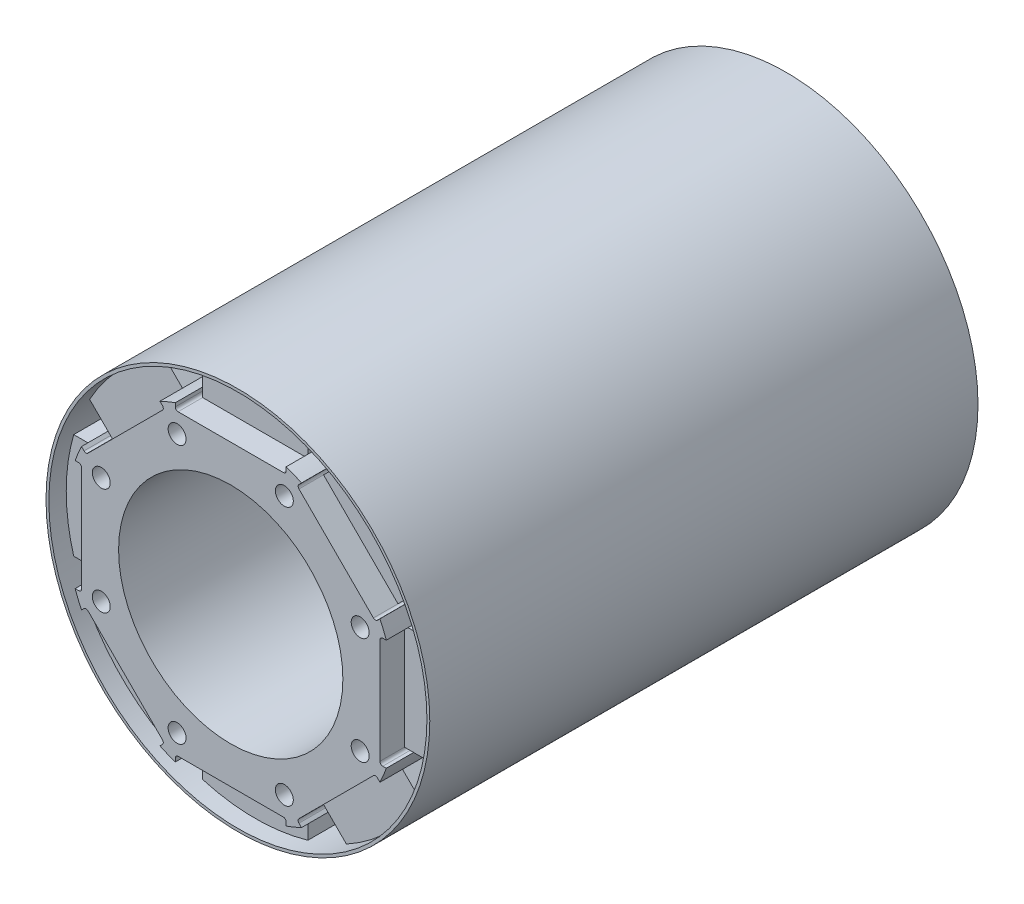
SolidWorks part; units mm, degrees
ref_plane "前视基准面" through (0, 0, 0) normal (0, 0, 1) x (1, 0, 0)
ref_plane "上视基准面" through (0, 0, 0) normal (0, 1, 0) x (1, 0, 0)
ref_plane "右视基准面" through (0, 0, 0) normal (1, 0, 0) x (0, 0, -1)
sketch "草图1" plane through (0, 0, 0) normal (0, 0, 1) x (1, 0, 0)
  circle A0 centre (0, 0) radius 14.735
  circle A1 centre (0, 0) radius 10.005
  dimension "D1" = 29.47
  dimension "D2" = 20.01
extrude "凸台-拉伸1" add sketch "草图1" along normal blind 50.19
ref_plane "基准面1" through (0, 0, 3) normal (0, 0, -1) x (-1, 0, 0)
sketch "草图3" plane through (0, 0, 3) normal (0, 0, -1) x (-1, 0, 0)
  line L0 (0, 17.0863) -> (0, -17.5115) construction
  line L1 (-4.9475, 13.8796) -> (-4.9475, 13.31)
  line L2 (-4.9475, 13.31) -> (4.9475, 13.31)
  line L3 (4.9475, 13.31) -> (4.9475, 13.8796)
  arc A0 (4.9475, 13.8796) -> (-4.9475, 13.8796) centre (0, 0) ccw
  dimension "D2" = 14.735
  dimension "D1" = 13.31
  dimension "D3" = 9.895
extrude "切除-拉伸1" cut sketch "草图3" against normal through all and the other way blind 42 contours L2 L3 A0 L1
ref_axis "基准轴1" through (0, 0, 50.19) along (0, 0, -1)
fillet "圆角1" radius 0.25 2 edges at (-4.9475, 13.31, 25.095) (4.9475, 13.31, 25.095)
pattern_circular "阵列(圆周)2" count 8 over 360 about axis through (0, 0, 50.19) along (0, 0, -1) of "圆角1", "切除-拉伸1"
sketch "草图4" plane through (0, 0, 3) normal (0, 0, -1) x (-1, 0, 0)
  line L0 (0, 0) -> (0, 19.0796) construction
  line L1 (-4.6975, 13.31) -> (-4.6975, 16.1976)
  line L2 (-4.6975, 13.31) -> (4.6975, 13.31)
  line L3 (4.6975, 13.31) -> (4.6975, 16.1976)
  arc A0 (4.6975, 16.1976) -> (-4.6975, 16.1976) centre (0, 0) ccw
  dimension "D1" = 33.73
extrude "凸台-拉伸2" add sketch "草图4" against normal blind 45
pattern_circular "阵列(圆周)4" count 8 over 360 about axis through (0, 0, 50.19) along (0, 0, -1) of "凸台-拉伸2"
ref_plane "基准面2" through (0, 0, 0.64) normal (0, 0, -1) x (-1, 0, 0)
sketch "草图5" plane through (0, 0, 0.64) normal (0, 0, -1) x (-1, 0, 0)
  circle A0 centre (0, 0) radius 16.865
  circle A1 centre (0, 0) radius 17.12
  dimension "D1" = 34.24
extrude "凸台-拉伸3" add sketch "草图5" against normal offset from surface (48.91 mm away) 0.64 up to face at (10.005, 0, 50.19)
hole_wizard "M2 螺纹孔2" positions "草图10" profile "草图9" tap size "M2" standard "GB"
sketch "草图10" plane through (0, 0, 50.19) normal (0, 0, 1) x (1, 0, 0)
  line L0 (0, 0) -> (0, 18.1698) construction
  line L2 (0, 0) -> (-7.5138, 18.1398) construction
  circle A0 centre (0, 0) radius 12.5 construction
  point P0 (-4.7835, 11.5485)
  dimension "D2" = 25
  dimension "D1" = 22.5
sketch "草图9" plane through (-4.7835, 11.5485, 50.19) normal (1, 0, 0) x (0, -1, 0)
  line L0 (0, 0) -> (0, 5.6807)
  line L1 (0, 5.6807) -> (0.8, 5.2)
  line L2 (0.8, 5.2) -> (0.8, 0)
  line L5 (0.8, 0) -> (0, 0)
  line L10 (0, 5.6807) -> (-0.8, 5.2) construction
  line L11 (0, -6.35) -> (0, 107.95) construction
  dimension "螺纹孔钻头直径" = 1.6
  dimension "螺纹孔钻头深度" = 5.2
  dimension "导头角度" = 118
cosmetic thread "孔螺蚊线2" parameters "D1"=4, "D2"=2
pattern_circular "阵列(圆周)6" count 8 over 360 about axis through (0, 0, 50.19) along (0, 0, -1) of "M2 螺纹孔2"
